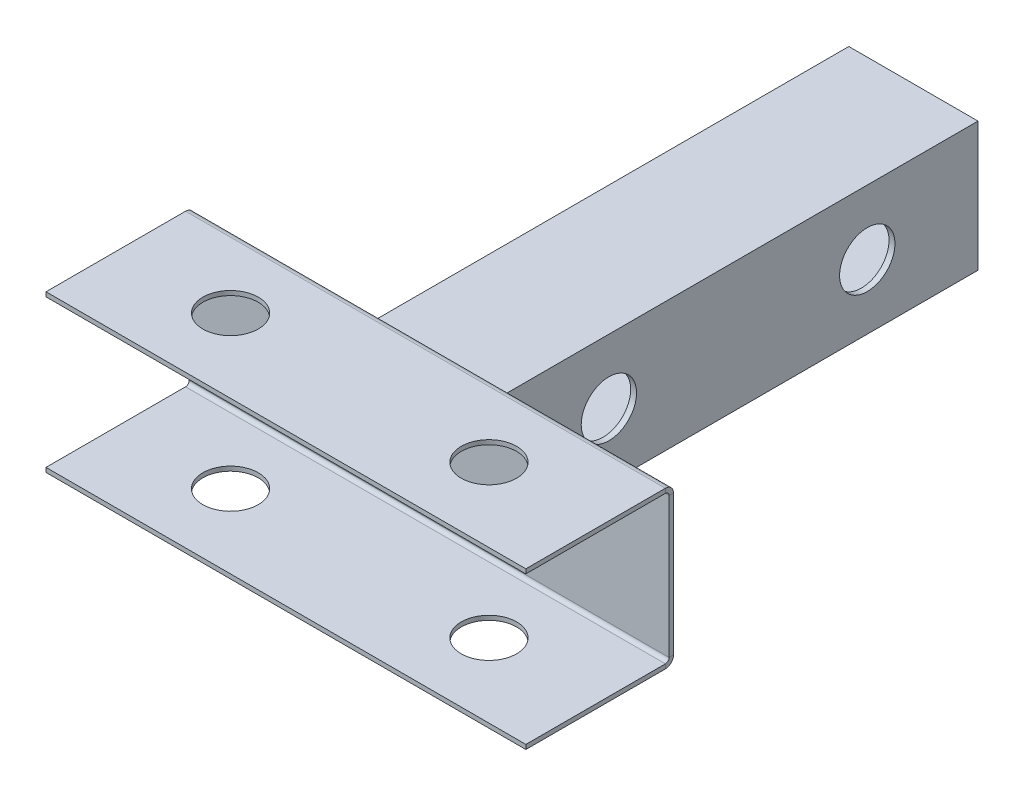
SolidWorks part; units mm, degrees
note: '?' marks a value the reader was unsure of. The reader was unsure of these and kept them because the rebuilt part matched: flange length of "Brida de arista1".
material "Acero al carbono no aleado"
ref_plane "Alzado" through (0, 0, 0) normal (0, 0, 1) x (1, 0, 0)
ref_plane "Planta" through (0, 0, 0) normal (0, 1, 0) x (1, 0, 0)
ref_plane "Vista lateral" through (0, 0, 0) normal (1, 0, 0) x (0, 0, -1)
sketch "Croquis1" plane through (0, 0, 0) normal (0, 1, 0) x (1, 0, 0)
  line L0 (0, -65) -> (0, 65)
  point P4 (0, 0)
  dimension "D1" = 130
other "Cuadrado 35X35X1.6(1)" corner treatment miter
ref_plane "Plano1" through (0, 0, 65) normal (0, 0, -1) x (-1, 0, 0)
sketch "Croquis11" plane through (0, 0, 65) normal (0, 0, -1) x (-1, 0, 0)
  line L0 (-15.9, -15.9) -> (-15.9, 15.9)
  line L1 (-17.5, -17.5) -> (17.5, -17.5)
  line L2 (-17.5, -17.5) -> (-17.5, 17.5)
  line L3 (-17.5, 17.5) -> (17.5, 17.5)
  line L4 (17.5, -17.5) -> (17.5, 17.5)
  line L5 (-17.5, -17.5) -> (17.5, 17.5) construction
  line L6 (-17.5, 17.5) -> (17.5, -17.5) construction
  line L7 (-15.9, 15.9) -> (15.9, 15.9)
  line L8 (15.9, -15.9) -> (15.9, 15.9)
  line L9 (-15.9, -15.9) -> (15.9, -15.9)
  point P0 (0, 0)
  point P10 (0, 17.5)
  point P11 (-17.5, 17.5)
  point P12 (17.5, 17.5)
  point P13 (17.5, -17.5)
  point P14 (-17.5, -17.5)
  point P15 (-17.5, 0)
  point P16 (17.5, 0)
  point P17 (0, -17.5)
  point P18 (0, 0)
  dimension "D1" = 35
  dimension "D2" = 35
  dimension "D3" = 1.6
sketch "Croquis12" plane through (-17.5, 0, 0) normal (-1, 0, 0) x (0, 0, 1)
  line L0 (-121.8307, 0) -> (108.6423, 0) construction
  line L1 (65, -17.5) -> (65, 17.5) construction
  line L2 (0, -92.6108) -> (0, 92.6108) construction
  circle A0 centre (35, 0) radius 7.5
  circle A1 centre (-35, 0) radius 7.5
  circle A2 centre (35, 0) radius 7.5 construction
  circle A3 centre (-35, 0) radius 7.5 construction
  point P12 (0, 0)
  dimension "D1" = 15
  dimension "D2" = 30
  dimension "D3" = 100
extrude "Cortar-Extruir1" cut sketch "Croquis12" against normal through all both and the other way through all
mirror "Simetría1" [suppressed] about plane through (0, 0, 0) normal (0, 0, 1)
sketch "Croquis14" plane through (0, 0, 65) normal (0, 0, 1) x (1, 0, 0)
  line L1 (-20, -65) -> (20, -65)
  line L2 (-20, -65) -> (-20, 65)
  line L3 (-20, 65) -> (20, 65)
  line L4 (20, -65) -> (20, 65)
  line L5 (-20, -65) -> (20, 65) construction
  line L6 (-20, 65) -> (20, -65) construction
  point P0 (0, 0)
  dimension "D1" = 40
  dimension "D2" = 130
ref_axis "Eje1" through (0, 0, 113.5) along (0, 0, -1)?
base flange "Brida base1" sketch "Croquis14" thickness 1.2 reverse thickness direction yes parameters "D1"=1
edge flange "Brida de arista1" sketch "Croquis24" flange profiles "Croquis24", "Croquis25" flange angle 90 flange length 40 flange position material outside bend radius 1 thickness 1.2 relief rectangular parameters "D6"=10, "D8"=1
sketch "Croquis24" plane through (20, 0, 66.2) normal (1, 0, 0) x (0, 1, 0)
  line L0 (-65, 0) -> (65, 0) construction
  line L1 (-65, 0) -> (65, 0)
  line L2 (-65, 0) -> (-65, 38.8)
  line L3 (-65, 38.8) -> (65, 38.8)
  line L4 (65, 38.8) -> (65, 0)
sketch "Croquis25" plane through (-20, 0, 66.2) normal (-1, 0, 0) x (0, -1, 0)
  line L0 (-65, 0) -> (65, 0) construction
  line L1 (-65, 0) -> (65, 0)
  line L2 (-65, 0) -> (-65, 38.8)
  line L3 (-65, 38.8) -> (65, 38.8)
  line L4 (65, 38.8) -> (65, 0)
bend "Pliegue de arista1" bend radius 1 bend angle 90 parameters "D5"=1
bend "Pliegue de arista2" bend radius 1 bend angle 90 parameters "D5"=2
sketch "Croquis26" plane through (-21.2, 0, 0) normal (-1, 0, 0) x (0, 0, 1)
  line L0 (85, 98.126) -> (85, -98.507) construction
  line L1 (65, -65) -> (65, 65) construction
  line L2 (105, -65) -> (105, 65) construction
  line L3 (0, 0) -> (140.3024, 0) construction
  circle A0 centre (85, 35) radius 7.5
  circle A1 centre (85, -35) radius 7.5
  dimension "D1" = 15
  dimension "D2" = 70
extrude "Cortar-Extruir2" cut sketch "Croquis26" against normal through all both and the other way through all
move or copy body "Sólido-Mover/Copiar1" bodies to move or copy 106 copy no rotation origin (0, 0, 0) rotation axis (0, 0, -1) rotation angle 90
sketch "Líneas de pliegue1" [suppressed] plane through (0, 0, 0) normal (0, 1, 0) x (1, 0, 0)
sketch "Cuadro delimitador1" [suppressed] plane through (0, 0, 0) normal (0, 1, 0) x (1, 0, 0)
sheet metal parameters "Chapa metálica4" thickness 1.2 parameters "D1"=1
flat pattern "Chapa desplegada4" [suppressed]
sketch "Líneas de pliegue2" plane through (0, 0, 0) normal (0, 1, 0) x (1, 0, 0)
sketch3d "Cuadro delimitador2" [suppressed]
  line L0 (20, 65, 0) -> (20, -65, 0) construction
  line L1 (-20, 65, 0) -> (-20, -65, 0) construction
  line L2 (20, 65, 0) -> (-20, 65, 0) construction
  line L3 (20, -65, 0) -> (-20, -65, 0) construction
sheet metal parameters "Chapa metálica5" thickness 1.2 parameters "D1"=1
flat pattern "Chapa desplegada4"
sketch "Líneas de pliegue2" plane through (0, 0, 65) normal (0, 0, -1) x (-1, 0, 0)
  line L0 (20.2566, -65) -> (20.2566, 65) construction
  line L1 (-20.2566, 65) -> (-20.2566, -65) construction
  line L2 (20.2566, -65) -> (20.2566, 65) construction
  line L3 (-20.2566, 65) -> (-20.2566, -65) construction
sketch3d "Cuadro delimitador2" [suppressed]
  line L0 (-59.3133, 65, 0) -> (-59.3133, -65, 0) construction
  line L1 (59.3133, 65, 0) -> (59.3133, -65, 0) construction
  line L2 (-59.3133, 65, 0) -> (59.3133, 65, 0) construction
  line L3 (-59.3133, -65, 0) -> (59.3133, -65, 0) construction
bend of the flat pattern "Aplanar-<Pliegue de arista1>1"
bend of the flat pattern "Aplanar-<Pliegue de arista2>1"
sheet metal parameters "Chapa metálica6" thickness 1.2 parameters "D1"=1
flat pattern "Chapa desplegada4"
sketch "Líneas de pliegue2" plane through (0, 0, 65) normal (0, 0, -1) x (-1, 0, 0)
  line L0 (20.2566, -65) -> (20.2566, 65) construction
  line L1 (-20.2566, 65) -> (-20.2566, -65) construction
  line L2 (20.2566, -65) -> (20.2566, 65) construction
  line L3 (-20.2566, 65) -> (-20.2566, -65) construction
sketch3d "Cuadro delimitador2" [suppressed]
  line L0 (-59.3133, 65, 0) -> (-59.3133, -65, 0) construction
  line L1 (59.3133, 65, 0) -> (59.3133, -65, 0) construction
  line L2 (-59.3133, 65, 0) -> (59.3133, 65, 0) construction
  line L3 (-59.3133, -65, 0) -> (59.3133, -65, 0) construction
bend of the flat pattern "Aplanar-<Pliegue de arista1>1"
bend of the flat pattern "Aplanar-<Pliegue de arista2>1"
sheet metal parameters "Chapa metálica7" thickness 1.2 parameters "D1"=1
flat pattern "Chapa desplegada4"
sketch "Líneas de pliegue2" plane through (0, 0, 65) normal (0, 0, -1) x (-1, 0, 0)
  line L0 (65, 20.2566) -> (-65, 20.2566) construction
  line L1 (-65, -20.2566) -> (65, -20.2566) construction
  line L2 (65, 20.2566) -> (-65, 20.2566) construction
  line L3 (-65, -20.2566) -> (65, -20.2566) construction
sketch3d "Cuadro delimitador2" [suppressed]
  line L0 (-65, -59.3133, 0) -> (65, -59.3133, 0) construction
  line L1 (-65, 59.3133, 0) -> (65, 59.3133, 0) construction
  line L2 (-65, -59.3133, 0) -> (-65, 59.3133, 0) construction
  line L3 (65, -59.3133, 0) -> (65, 59.3133, 0) construction
bend of the flat pattern "Aplanar-<Pliegue de arista1>1"
bend of the flat pattern "Aplanar-<Pliegue de arista2>1"
